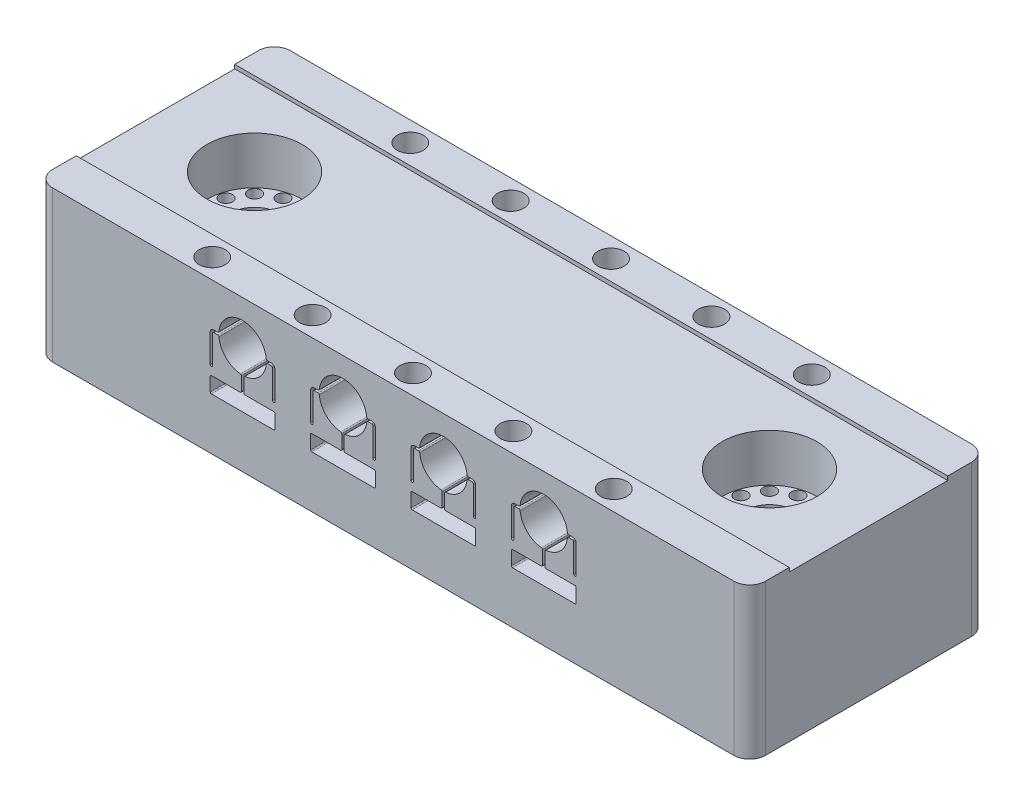
SolidWorks part; units mm, degrees
ref_plane "Front Plane" through (0, 0, 0) normal (0, 0, 1) x (1, 0, 0)
ref_plane "Top Plane" through (0, 0, 0) normal (0, 1, 0) x (1, 0, 0)
ref_plane "Right Plane" through (0, 0, 0) normal (1, 0, 0) x (0, 0, -1)
sketch "Sketch1" plane through (0, 0, 0) normal (0, 1, 0) x (1, 0, 0)
  line L0 (-45, 13) -> (-45, -13)
  line L3 (-43, -15) -> (43, -15)
  line L4 (45, -13) -> (45, 13)
  line L5 (43, 15) -> (-43, 15)
  line L6 (-32.5, 0) -> (32.5, 0) construction
  line L8 (-33.8159, 4.9109) -> (-36.095, 3.595) construction
  line L9 (-36.095, 3.595) -> (-37.4109, 1.3159) construction
  line L10 (-37.4109, 1.3159) -> (-37.4109, -1.3159) construction
  line L11 (-37.4109, -1.3159) -> (-36.095, -3.595) construction
  line L12 (-36.095, -3.595) -> (-33.8159, -4.9109) construction
  line L13 (-33.8159, -4.9109) -> (-31.1841, -4.9109) construction
  line L14 (-31.1841, -4.9109) -> (-28.905, -3.595) construction
  line L15 (-28.905, -3.595) -> (-27.5891, -1.3159) construction
  line L16 (-27.5891, -1.3159) -> (-27.5891, 1.3159) construction
  line L17 (-27.5891, 1.3159) -> (-28.905, 3.595) construction
  line L18 (-28.905, 3.595) -> (-31.1841, 4.9109) construction
  line L19 (-31.1841, 4.9109) -> (-33.8159, 4.9109) construction
  line L20 (33.8159, 4.9109) -> (31.1841, 4.9109) construction
  line L21 (31.1841, 4.9109) -> (28.905, 3.595) construction
  line L22 (28.905, 3.595) -> (27.5891, 1.3159) construction
  line L23 (27.5891, 1.3159) -> (27.5891, -1.3159) construction
  line L24 (27.5891, -1.3159) -> (28.905, -3.595) construction
  line L25 (28.905, -3.595) -> (31.1841, -4.9109) construction
  line L26 (31.1841, -4.9109) -> (33.8159, -4.9109) construction
  line L27 (33.8159, -4.9109) -> (36.095, -3.595) construction
  line L28 (36.095, -3.595) -> (37.4109, -1.3159) construction
  line L29 (37.4109, -1.3159) -> (37.4109, 1.3159) construction
  line L30 (37.4109, 1.3159) -> (36.095, 3.595) construction
  line L31 (36.095, 3.595) -> (33.8159, 4.9109) construction
  circle A2 centre (-32.5, 0) radius 3
  circle A3 centre (32.5, 0) radius 3
  circle A17 centre (32.5, 0) radius 6 construction
  circle A18 centre (-32.5, 0) radius 6 construction
  circle A19 centre (-31.1841, 4.9109) radius 0.9159 construction
  circle A20 centre (-31.1841, 4.9109) radius 0.8159
  circle A21 centre (-32.5, 0) radius 4.9109 construction
  circle A22 centre (-33.8159, 4.9109) radius 0.8159
  circle A23 centre (-33.8159, 4.9109) radius 1.8159 construction
  circle A24 centre (-36.095, 3.595) radius 0.8159
  circle A25 centre (-37.4109, 1.3159) radius 0.8159
  circle A26 centre (-37.4109, -1.3159) radius 0.8159
  circle A27 centre (-36.095, -3.595) radius 0.8159
  circle A28 centre (-33.8159, -4.9109) radius 0.8159
  circle A29 centre (-31.1841, -4.9109) radius 0.8159
  circle A30 centre (-28.905, -3.595) radius 0.8159
  circle A31 centre (-27.5891, -1.3159) radius 0.8159
  circle A32 centre (-27.5891, 1.3159) radius 0.8159
  circle A33 centre (-28.905, 3.595) radius 0.8159
  circle A34 centre (32.5, 0) radius 4.9109 construction
  circle A35 centre (31.1841, 4.9109) radius 0.8159
  circle A36 centre (33.8159, 4.9109) radius 0.8159
  circle A37 centre (36.095, 3.595) radius 0.8159
  circle A38 centre (37.4109, 1.3159) radius 0.8159
  circle A39 centre (37.4109, -1.3159) radius 0.8159
  circle A40 centre (36.095, -3.595) radius 0.8159
  circle A41 centre (33.8159, -4.9109) radius 0.8159
  circle A42 centre (31.1841, -4.9109) radius 0.8159
  circle A43 centre (28.905, -3.595) radius 0.8159
  circle A44 centre (27.5891, -1.3159) radius 0.8159
  circle A45 centre (27.5891, 1.3159) radius 0.8159
  circle A46 centre (28.905, 3.595) radius 0.8159
  arc A47 (43, -15) -> (45, -13) centre (43, -13) ccw
  arc A48 (-45, -13) -> (-43, -15) centre (-43, -13) ccw
  arc A49 (-45, 13) -> (-43, 15) centre (-43, 13) cw
  arc A50 (45, 13) -> (43, 15) centre (43, 13) ccw
  point P2 (-45, 0)
  point P6 (0, 15)
  point P72 (-45, 15)
  point P75 (45, 15)
  dimension "D1" = 90
  dimension "D2" = 12
  dimension "D3" = 65
  dimension "D4" = 6
  dimension "D5" = 30
  dimension "D6" = 0.1
  dimension "D7" = 1.6317
  dimension "D8" = 1
  dimension "D9" = 2
extrude "Boss-Extrude1" add sketch "Sketch1" along normal blind 19.05
sketch "Sketch2" plane through (0, 19.05, 0) normal (0, 1, 0) x (1, 0, 0)
  circle A0 centre (32.5, 0) radius 6 construction
  circle A1 centre (-32.5, 0) radius 6 construction
  circle A2 centre (32.5, 0) radius 6
  circle A3 centre (-32.5, 0) radius 6
extrude "Cut-Extrude1" cut sketch "Sketch2" against normal blind 6.5
sketch "Sketch3" plane through (0, 0, 15) normal (0, 0, 1) x (1, 0, 0)
  line L0 (0, 19.05) -> (0, 13.55) construction
  line L1 (-43, 19.05) -> (43, 19.05) construction
  line L2 (-22.1427, 13.7) -> (-22.6427, 13.7)
  line L3 (-22.1427, 13.4) -> (-22.6427, 13.4)
  line L4 (-23.0927, 13.25) -> (-23.0927, 9.7)
  line L5 (-22.7927, 13.25) -> (-22.7927, 9.7)
  line L6 (-15.8714, 13.7) -> (-15.3714, 13.7)
  line L7 (-15.8714, 13.4) -> (-15.3714, 13.4)
  line L8 (-15.2214, 13.25) -> (-15.2214, 9.7)
  line L9 (-14.9214, 13.25) -> (-14.9214, 9.7)
  line L10 (-19.157, 10.4143) -> (-19.157, 8.7)
  line L11 (-19.307, 8.55) -> (-22.9427, 8.55)
  line L12 (-18.857, 10.4143) -> (-18.857, 8.7)
  line L13 (-18.707, 8.55) -> (-15.0714, 8.55)
  line L14 (-22.9427, 6.5478) -> (-15.0714, 6.5478)
  line L15 (-23.0927, 8.4) -> (-23.0927, 6.6978)
  line L16 (-14.9214, 8.4) -> (-14.9214, 6.6978)
  line L17 (-19.007, 16.55) -> (-19.007, 19.05) construction
  line L18 (-22.1427, 13.4) -> (-22.1427, 13.7) construction
  line L19 (-22.9427, 9.55) -> (-22.9427, 8.55) construction
  line L20 (-19.157, 10.4143) -> (-18.857, 10.4143) construction
  line L21 (-21.507, 6.5478) -> (-21.507, 0) construction
  line L22 (-43, 0) -> (43, 0) construction
  line L23 (-16.507, 6.5478) -> (-16.507, 0) construction
  line L24 (-21.507, 3.2739) -> (-16.507, 3.2739) construction
  line L25 (-19.007, 3.2739) -> (-19.007, 6.5478) construction
  line L26 (-19.007, 8.55) -> (-19.007, 10.55) construction
  line L27 (-21.507, 6.5478) -> (-19.007, 8.05) construction
  line L28 (-19.007, 8.05) -> (-16.507, 6.5478) construction
  line L29 (-19.007, 13.55) -> (-14.9214, 13.55) construction
  line L30 (-14.9214, 13.55) -> (-10.4214, 13.55) construction
  line L31 (-10.4214, 13.55) -> (-6.3357, 13.55) construction
  line L32 (-6.3357, 13.55) -> (-2.25, 13.55) construction
  line L33 (-2.25, 13.55) -> (2.25, 13.55) construction
  line L34 (2.25, 13.55) -> (6.3357, 13.55) construction
  line L35 (6.3357, 13.55) -> (10.4214, 13.55) construction
  line L36 (10.4214, 13.55) -> (14.9214, 13.55) construction
  line L37 (14.9214, 13.55) -> (19.007, 13.55) construction
  arc A0 (-21.9934, 13.2643) -> (-19.2928, 10.5636) centre (-19.007, 13.55) ccw
  arc A1 (-22.6427, 13.7) -> (-23.0927, 13.25) centre (-22.6427, 13.25) ccw
  arc A2 (-22.6427, 13.4) -> (-22.7927, 13.25) centre (-22.6427, 13.25) ccw
  arc A3 (-23.0927, 9.7) -> (-22.7927, 9.7) centre (-22.9427, 9.7) ccw
  arc A4 (-15.3714, 13.7) -> (-14.9214, 13.25) centre (-15.3714, 13.25) cw
  arc A5 (-15.3714, 13.4) -> (-15.2214, 13.25) centre (-15.3714, 13.25) cw
  arc A6 (-15.2214, 9.7) -> (-14.9214, 9.7) centre (-15.0714, 9.7) ccw
  arc A7 (-16.0207, 13.8357) -> (-21.9934, 13.8357) centre (-19.007, 13.55) ccw
  arc A8 (-15.8714, 13.7) -> (-16.0207, 13.8357) centre (-15.8714, 13.85) cw
  arc A9 (-15.8714, 13.4) -> (-16.0207, 13.2643) centre (-15.8714, 13.25) ccw
  arc A10 (-22.1427, 13.4) -> (-21.9934, 13.2643) centre (-22.1427, 13.25) cw
  arc A11 (-22.1427, 13.7) -> (-21.9934, 13.8357) centre (-22.1427, 13.85) ccw
  arc A12 (-18.7213, 10.5636) -> (-16.0207, 13.2643) centre (-19.007, 13.55) ccw
  arc A13 (-19.157, 8.7) -> (-19.307, 8.55) centre (-19.307, 8.7) cw
  arc A14 (-22.9427, 8.55) -> (-23.0927, 8.4) centre (-22.9427, 8.4) ccw
  arc A15 (-23.0927, 6.6978) -> (-22.9427, 6.5478) centre (-22.9427, 6.6978) ccw
  arc A16 (-14.9214, 6.6978) -> (-15.0714, 6.5478) centre (-15.0714, 6.6978) cw
  arc A17 (-15.0714, 8.55) -> (-14.9214, 8.4) centre (-15.0714, 8.4) cw
  arc A18 (-18.857, 8.7) -> (-18.707, 8.55) centre (-18.707, 8.7) ccw
  arc A19 (-18.857, 10.4143) -> (-18.7213, 10.5636) centre (-18.707, 10.4143) cw
  arc A20 (-19.157, 10.4143) -> (-19.2928, 10.5636) centre (-19.307, 10.4143) ccw
  point P30 (-16.0108, 13.7)
  point P59 (-18.857, 10.5538)
  dimension "D1" = 2.5
  dimension "D2" = 1
  dimension "D5" = 3
  dimension "D3" = 0.3
  dimension "D4" = 5
  dimension "D6" = 2
  dimension "D7" = 118
  dimension "D8" = 0.5
  dimension "D9" = 0.5
  dimension "D10" = 4.5
extrude "Cut-Extrude2" cut sketch "Sketch3" against normal through all
pattern_linear "LPattern1" count 4 spacing 12.6714 along (1, 0, 0) of "Cut-Extrude2"
sketch "Sketch4" plane through (0, 19.05, 0) normal (0, 1, 0) x (1, 0, 0)
  line L0 (-45, -10) -> (45, -10)
  line L1 (-45, 13) -> (-45, -13) construction
  line L2 (45, -13) -> (45, 13) construction
  line L3 (45, -10) -> (45, 10)
  line L4 (45, 10) -> (-45, 10)
  line L5 (-45, 10) -> (-45, -10)
  line L6 (10.4214, -15) -> (14.9214, -15) construction
  line L7 (-2.25, -15) -> (2.25, -15) construction
  line L8 (-14.9214, -15) -> (-10.4214, -15) construction
  line L9 (10.4214, -15) -> (14.9214, -15) construction
  line L10 (-2.25, -15) -> (2.25, -15) construction
  line L11 (-14.9214, -15) -> (-10.4214, -15) construction
  line L12 (-14.9214, -15) -> (-23.0927, -15) construction
  line L13 (-43, -15) -> (43, -15) construction
  line L14 (-23.0927, -15) -> (-27.5927, -15) construction
  line L15 (-10.4214, -15) -> (-2.25, -15) construction
  line L16 (-25.3427, -15) -> (-25.3427, -10) construction
  line L17 (-25.3427, 10) -> (-25.3427, 15) construction
  line L18 (43, 15) -> (-43, 15) construction
  line L20 (14.9214, -15) -> (23.0927, -15) construction
  line L21 (23.0927, -15) -> (27.5927, -15) construction
  line L22 (25.3427, -15) -> (25.3427, -10) construction
  circle A0 centre (-25.3427, -12.5) radius 2.5 construction
  circle A1 centre (-25.3427, -12.5) radius 2 construction
  circle A2 centre (-25.3427, 12.5) radius 2.5 construction
  circle A3 centre (-25.3427, 12.5) radius 2 construction
  point P9 (-45, 0)
  point P21 (25.3427, -12.5)
  dimension "D1" = 0.5
  dimension "D2" = 4
sketch "Sketch5" plane through (0, 19.05, 0) normal (0, 1, 0) x (1, 0, 0)
  point P0 (-25.3427, -12.5)
  point P3 (-25.3427, 12.5)
hole_wizard "M4x0.7 Tapped Hole1" positions "Sketch5" profile "Sketch6" tap size "M4x0.7" standard "ANSI Metric"
sketch "Sketch6" plane through (-25.3427, 19.05, 12.5) normal (1, 0, 0) x (0, 0, 1)
  line L0 (0, 0) -> (0, 11.0914)
  line L1 (0, 11.0914) -> (1.65, 10.1)
  line L2 (1.65, 10.1) -> (1.65, 0)
  line L5 (1.65, 0) -> (0, 0)
  line L10 (0, 11.0914) -> (-1.65, 10.1) construction
  line L11 (0, -6.35) -> (0, 107.95) construction
  dimension "Tap Drill Dia." = 3.3
  dimension "Tap Drill Depth" = 10.1
  dimension "Drill Angle" = 118
cosmetic thread "Hole Thread1" parameters "D1"=8, "D2"=4
cosmetic thread "Hole Thread2" parameters "D1"=8, "D2"=4
pattern_linear "LPattern2" count 5 spacing 12.6714 along (1, 0, 0) of "M4x0.7 Tapped Hole1"
cosmetic thread "Hole Thread3" parameters "D1"=8, "D2"=4
cosmetic thread "Hole Thread4" parameters "D1"=8, "D2"=4
cosmetic thread "Hole Thread5" parameters "D1"=8, "D2"=4
cosmetic thread "Hole Thread6" parameters "D1"=8, "D2"=4
cosmetic thread "Hole Thread7" parameters "D1"=8, "D2"=4
cosmetic thread "Hole Thread8" parameters "D1"=8, "D2"=4
cosmetic thread "Hole Thread9" parameters "D1"=8, "D2"=4
cosmetic thread "Hole Thread10" parameters "D1"=8, "D2"=4
extrude "Cut-Extrude3" cut sketch "Sketch4" against normal blind 0.5
sketch "Sketch7" plane through (0, 0, 0) normal (0, -1, 0) x (1, 0, 0)
  line L0 (-22.9427, 15) -> (-15.0714, 15) construction
  line L1 (-22.9427, 15) -> (-15.0714, 15) construction
  line L2 (15.0714, 15) -> (22.9427, 15) construction
  line L3 (15.0714, 15) -> (22.9427, 15) construction
  line L4 (-19.007, 5) -> (-19.007, -5) construction
  circle A0 centre (-19.007, 5) radius 2.5
  circle A1 centre (-19.007, -5) radius 2.5
  point P6 (-19.007, 15)
  point P7 (19.007, 15)
  point P8 (-19.007, 0)
  dimension "D2" = 5
  dimension "D1" = 10
extrude "Cut-Extrude4" cut sketch "Sketch7" against normal up to surface (6.5478 mm away) up to face at (-19.007, 6.5478, 0)
pattern_linear "LPattern3" count 4 spacing 12.6714 along (1, 0, 0) of "Cut-Extrude4"
